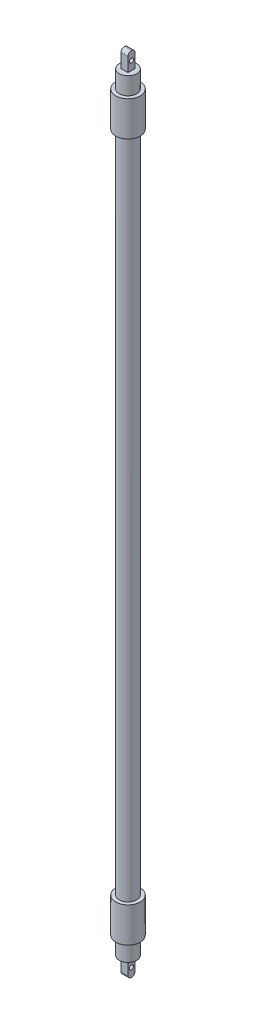
SolidWorks part; units mm, degrees
material "ABS"
ref_plane "Alzado" through (0, 0, 0) normal (0, 0, 1) x (1, 0, 0)
ref_plane "Planta" through (0, 0, 0) normal (0, 1, 0) x (1, 0, 0)
ref_plane "Vista lateral" through (0, 0, 0) normal (1, 0, 0) x (0, 0, -1)
sketch "Croquis1" plane through (0, 0, 0) normal (0, 1, 0) x (1, 0, 0)
  circle A0 centre (0, 0) radius 2.5
extrude "Saliente-Extruir6" add sketch "Croquis1" along normal blind 190
sketch "Croquis4" plane through (0, 190, 0) normal (0, 1, 0) x (1, 0, 0)
  circle A0 centre (0, 0) radius 3.5
extrude "Saliente-Extruir7" add sketch "Croquis4" along normal blind 10
sketch "Croquis5" plane through (0, 200, 0) normal (0, 1, 0) x (1, 0, 0)
  circle A0 centre (0, 0) radius 2.5
extrude "Saliente-Extruir9" add sketch "Croquis5" along normal blind 5
sketch "Croquis6" plane through (0, 0, 0) normal (0, -1, 0) x (1, 0, 0)
  circle A0 centre (0, 0) radius 3.5
extrude "Saliente-Extruir10" add sketch "Croquis6" along normal blind 10
sketch "Croquis7" plane through (0, -10, 0) normal (0, -1, 0) x (1, 0, 0)
  circle A0 centre (0, 0) radius 2.5
extrude "Saliente-Extruir11" add sketch "Croquis7" along normal blind 5
sketch "Croquis8" plane through (0, 0, 0) normal (0, 0, 1) x (1, 0, 0)
  line L0 (0, 205) -> (-1, 205)
  line L1 (2.5, 205) -> (-2.5, 205) construction
  line L2 (0, 205) -> (1, 205)
  line L3 (1, 205) -> (1, 210)
  line L4 (1, 210) -> (-1, 210)
  line L5 (-1, 210) -> (-1, 205)
  line L6 (-2.5, 95) -> (-38.3602, 95)
  line L7 (-2.5, 190) -> (-2.5, 0) construction
  line L8 (-1, -20) -> (-1, -15)
  line L9 (1, -20) -> (-1, -20)
  line L10 (1, -15) -> (1, -20)
  line L11 (0, -15) -> (1, -15)
  line L12 (0, -15) -> (-1, -15)
  dimension "D1" = 5
extrude "Saliente-Extruir12" add sketch "Croquis8" along normal mid plane 2 contours L4 L5 L0 L2 L3 | L11 L12 L8 L9 L10 region at (0, 207.5, 0) region at (0, -17.5, 0)
sketch "Croquis10" plane through (0, 0, 0) normal (1, 0, 0) x (0, 0, -1)
  line L0 (2.5, 95) -> (26.9457, 95)
  line L1 (2.5, 0) -> (2.5, 190) construction
  circle A0 centre (0, -17.5) radius 0.6
  circle A1 centre (0, 207.5) radius 0.6
extrude "Cortar-Extruir1" cut sketch "Croquis10" against normal mid plane 25 contours A0 | A1 region at (0, -17.5, 0) region at (0, 207.5, 0)
fillet "Redondeo3" radius 1 1 edges at (0, -20, 1)
fillet "Redondeo4" radius 1 3 edges at (0, 210, 1) (0, 210, -1) (0, -20, -1)
